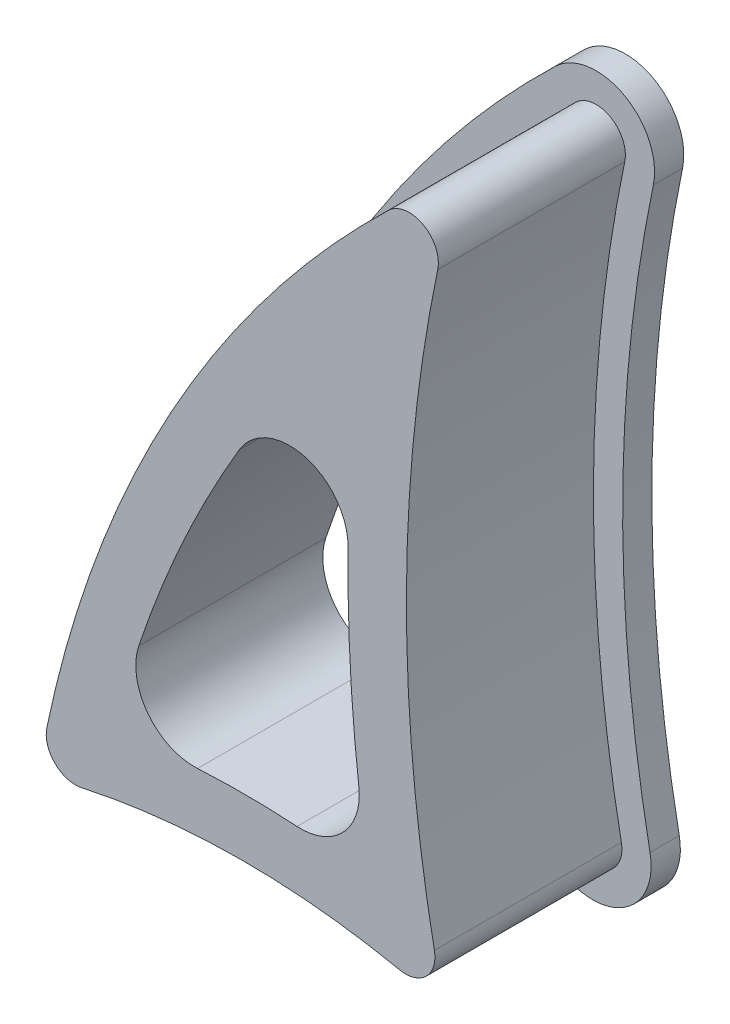
SolidWorks part; units mm, degrees
ref_plane "前视基准面" through (0, 0, 0) normal (0, 0, 1) x (1, 0, 0)
ref_plane "上视基准面" through (0, 0, 0) normal (0, 1, 0) x (1, 0, 0)
ref_plane "右视基准面" through (0, 0, 0) normal (1, 0, 0) x (0, 0, -1)
other "Configuration Table"
sketch "草图1" plane through (0, 0, 0) normal (0, 0, 1) x (1, 0, 0)
  line L0 (-42.4945, 0) -> (51.4094, 0) construction
  line L1 (0, -29.5679) -> (0, 45.0204) construction
  arc A0 (-13.5803, 0.8256) -> (-3.1148, 0.8674) centre (-8.25, -23.5995) cw
  arc A1 (-0.7415, 3.2104) -> (-0.6286, 23.0494) centre (48.3203, 12.851) cw
  arc A2 (-3.9737, 24.8981) -> (-15.9649, 3.1865) centre (25.1569, -5.3576) ccw
  arc A3 (-3.1148, 0.8674) -> (-0.7415, 3.2104) centre (-2.7039, 2.8247) ccw
  arc A4 (-13.5803, 0.8256) -> (-15.9649, 3.1865) centre (-14.0067, 2.7796) cw
  arc A5 (-0.6286, 23.0494) -> (-3.9737, 24.8981) centre (-2.5865, 23.4574) ccw
  arc A6 (-3.2801, 24.1777) -> (-14.9858, 2.9831) centre (25.1569, -5.3576) ccw
  arc A7 (-13.7935, 1.8026) -> (-14.9858, 2.9831) centre (-14.0067, 2.7796) cw
  arc A8 (-13.7935, 1.8026) -> (-2.9094, 1.8461) centre (-8.25, -23.5995) cw
  arc A9 (-2.9094, 1.8461) -> (-1.7227, 3.0175) centre (-2.7039, 2.8247) ccw
  arc A10 (-1.7227, 3.0175) -> (-1.6076, 23.2534) centre (48.3203, 12.851) cw
  arc A11 (-1.6076, 23.2534) -> (-3.2801, 24.1777) centre (-2.5865, 23.4574) ccw
  arc A12 (-8.3965, 14.5212) -> (-11.8383, 6.9858) centre (25.1569, -5.3576) ccw
  arc A14 (-9.8283, 4.356) -> (-6.423, 4.3408) centre (-8.25, -23.5995) cw
  arc A16 (-4.3066, 6.5734) -> (-4.676, 13.4781) centre (48.3203, 12.851) cw
  arc A18 (-3.9469, 4.0678) -> (-4.1417, 20.3832) centre (48.3203, 12.851) cw construction
  arc A19 (-4.1417, 20.3832) -> (-12.6925, 4.0458) centre (25.1569, -5.3576) ccw construction
  arc A20 (-4.676, 13.4781) -> (-8.3965, 14.5212) centre (-6.6759, 13.5018) ccw
  arc A21 (-4.1417, 20.3832) -> (-4.1417, 20.3832) centre (-4.1417, 20.3832) ccw construction
  arc A22 (-12.6925, 4.0458) -> (-3.9469, 4.0678) centre (-8.25, -23.5995) cw construction
  arc A23 (-9.8283, 4.356) -> (-11.8383, 6.9858) centre (-9.9411, 6.3528) cw
  arc A24 (-12.6925, 4.0458) -> (-12.6925, 4.0458) centre (-12.6925, 4.0458) cw construction
  arc A25 (-6.423, 4.3408) -> (-4.3066, 6.5734) centre (-6.2925, 6.3365) ccw
  arc A26 (-3.9469, 4.0678) -> (-3.9469, 4.0678) centre (-3.9469, 4.0678) ccw construction
  point P14 (0, 0)
  point P17 (-16.5, 0)
  point P20 (1, 29)
  dimension "D2" = 50
  dimension "D3" = 25
  dimension "D6" = 42
  dimension "D7" = 2
  dimension "D8" = 2
  dimension "D9" = 2
  dimension "D12" = 2
  dimension "D13" = 2
  dimension "D14" = 2
  dimension "D1" = 16.5
  dimension "D4" = 29
  dimension "D5" = 17.5
  dimension "D10" = 1
  dimension "D11" = 2
extrude "凸台-拉伸1" add sketch "草图1" along normal blind 6.4 contours A10 A11 A6 A7 A8 A9 A25 A14 A23 A12 A20 A16 region at (-2.2303, 24.102, 0)
extrude "凸台-拉伸2" add sketch "草图1<5>" against normal blind 1 separate body contours A1 A5 A2 A4 A0 A3 A11 A10 A9 A8 A7 A6 region at (-15.2091, 1.5652, 0)
sketch "草图1<5>" plane through (0, 0, 0) normal (0, 0, 1) x (1, 0, 0) same geometry as "草图1"
